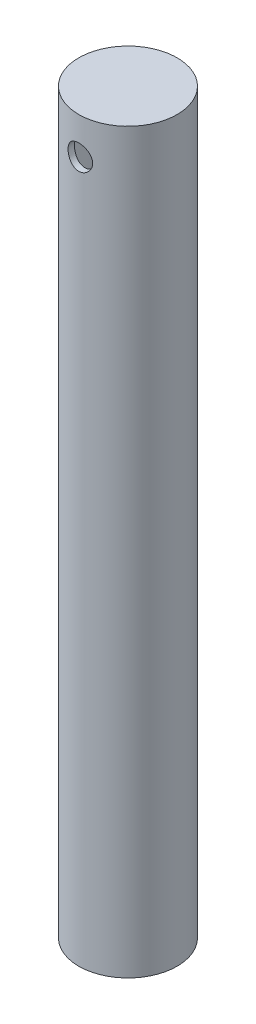
SolidWorks part; units mm, degrees
ref_plane "Front Plane" through (0, 0, 0) normal (0, 0, 1) x (1, 0, 0)
ref_plane "Top Plane" through (0, 0, 0) normal (0, 1, 0) x (1, 0, 0)
ref_plane "Right Plane" through (0, 0, 0) normal (1, 0, 0) x (0, 0, -1)
sketch "Sketch1" plane through (0, 0, 0) normal (0, 1, 0) x (1, 0, 0)
  circle A0 centre (0, 0) radius 40
  dimension "D1" = 80
extrude "Boss-Extrude1" add sketch "Sketch1" along normal blind 600
shell "Shell7" thickness 5
sketch "Sketch2" plane through (0, 0, 0) normal (0, 0, 1) x (1, 0, 0)
  line L0 (40, 600) -> (-40, 600) construction
  circle A0 centre (0, 570) radius 10
  dimension "D1" = 20
  dimension "D2" = 30
extrude "Cut-Extrude2" cut sketch "Sketch2" against normal blind 40 and the other way blind 40
